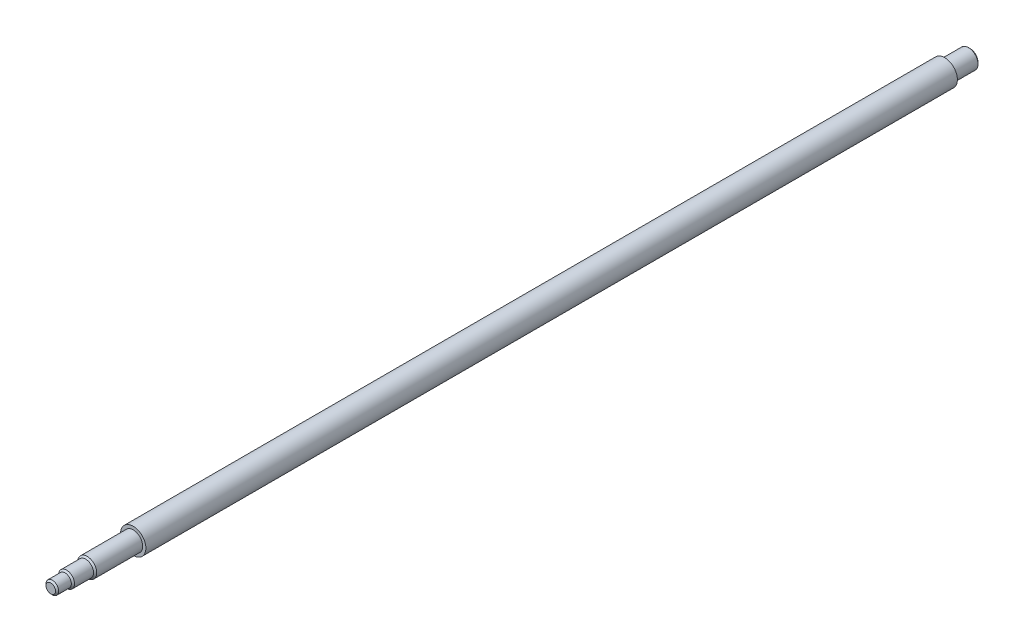
SolidWorks part; units mm, degrees
material "1.0037 (S235JR)"
ref_plane "Płaszczyzna przednia" through (0, 0, 0) normal (0, 0, 1) x (1, 0, 0)
ref_plane "Płaszczyzna górna" through (0, 0, 0) normal (0, 1, 0) x (1, 0, 0)
ref_plane "Płaszczyzna prawa" through (0, 0, 0) normal (1, 0, 0) x (0, 0, -1)
sketch "Szkic1" plane through (0, 0, 0) normal (1, 0, 0) x (0, 0, -1)
  line L0 (0, 0) -> (580, 0)
  line L1 (580, 0) -> (580, 6)
  line L2 (580, 6) -> (564, 6)
  line L3 (564, 6) -> (564, 8)
  line L4 (564, 8) -> (52, 8)
  line L5 (52, 8) -> (52, 6)
  line L6 (52, 6) -> (22, 6)
  line L7 (22, 6) -> (22, 5)
  line L8 (22, 5) -> (9, 5)
  line L9 (0, 4) -> (0, 0)
  line L10 (0, 4) -> (9, 4)
  line L11 (9, 4) -> (9, 5)
  dimension "D1" = 580
  dimension "D2" = 6
  dimension "D3" = 5
  dimension "D4" = 6
  dimension "D5" = 8
  dimension "D6" = 16
  dimension "D7" = 30
  dimension "D8" = 13
  dimension "D9" = 9
  dimension "D10" = 4
revolve "Obrót1" add sketch "Szkic1" angle 360 about L0
chamfer "Sfazowanie1" distance 1 angle 45 3 edges at (4, 0, 0) (5, 0, -9) (6, 0, -22)
chamfer "Sfazowanie2" distance 1 angle 45 1 edges at (6, 0, -580)
